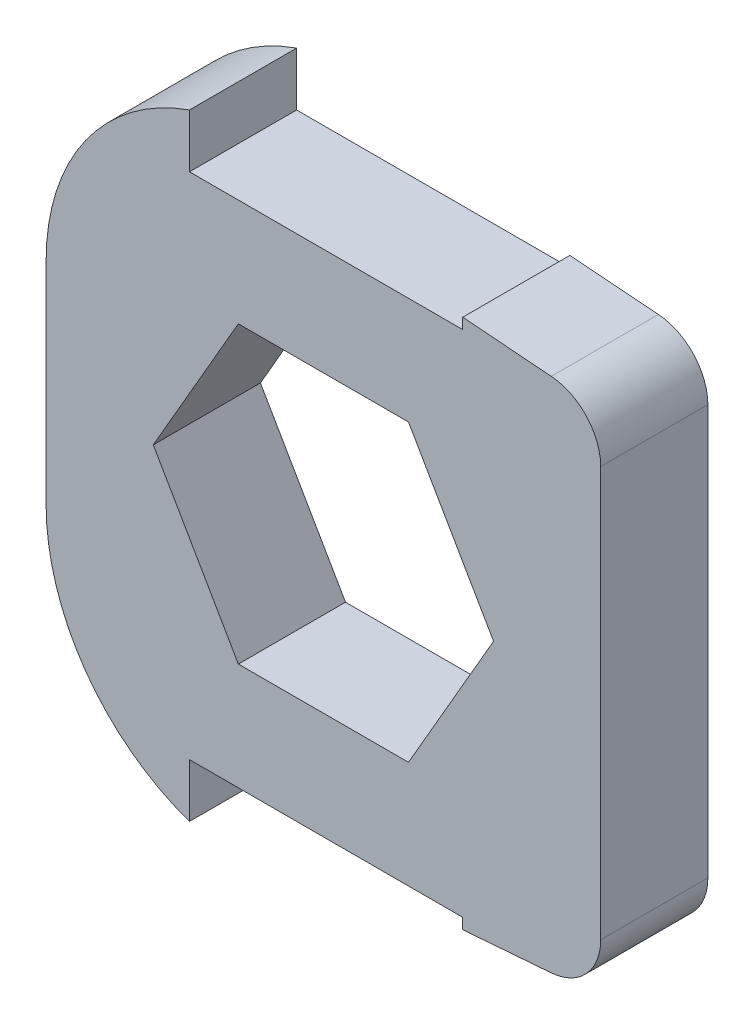
SolidWorks part; units mm, degrees
ref_plane "Plan de face" through (0, 0, 0) normal (0, 0, 1) x (1, 0, 0)
ref_plane "Plan de dessus" through (0, 0, 0) normal (0, 1, 0) x (1, 0, 0)
ref_plane "Plan de droite" through (0, 0, 0) normal (1, 0, 0) x (0, 0, -1)
sketch "Esquisse1" plane through (0, 0, 0) normal (0, 0, 1) x (1, 0, 0)
  line L0 (0, 5.75) -> (2.6754, 5.75)
  line L1 (2.6754, 5.75) -> (2.6754, 4.75)
  line L2 (2.6754, 4.75) -> (10.3509, 4.75) construction
  line L3 (10.3509, 4.75) -> (10.3509, -4.75)
  line L4 (10.3509, -4.75) -> (2.6754, -4.75) construction
  line L5 (2.6754, -4.75) -> (2.6754, -5.75)
  line L6 (2.6754, -5.75) -> (0, -5.75)
  line L7 (0, -5.75) -> (0, 5.75)
  line L8 (0, 0) -> (10.3509, 0) construction
  line L9 (10.3509, 4.75) -> (7.7754, 4.95)
  line L10 (2, 0) -> (3.5877, -2.75)
  line L11 (3.5877, -2.75) -> (6.7631, -2.75)
  line L12 (6.7631, -2.75) -> (8.3509, 0)
  line L13 (8.3509, 0) -> (6.7631, 2.75)
  line L14 (6.7631, 2.75) -> (3.5877, 2.75)
  line L15 (3.5877, 2.75) -> (2, 0)
  line L16 (7.7754, 4.95) -> (7.7754, 4.75)
  line L17 (7.7754, 4.75) -> (2.6754, 4.75)
  line L18 (7.7754, -4.75) -> (2.6754, -4.75)
  line L19 (7.7754, -4.95) -> (7.7754, -4.75)
  line L20 (10.3509, -4.75) -> (7.7754, -4.95)
  circle A0 centre (5.1754, 0) radius 2.75 construction
  point P22 (0, 0)
  dimension "D1" = 5.5
  dimension "D2" = 2
  dimension "D3" = 2.5
  dimension "D4" = 2
  dimension "D5" = 1
  dimension "D6" = 2
  dimension "D7" = 6.3509
  dimension "D8" = 5.1
  dimension "D9" = 0.2
  dimension "D10" = 9.5
extrude "Boss.-Extru.1" add sketch "Esquisse1" along normal blind 2
fillet "Congé1" radius 4 2 edges at (0, -5.75, 1) (0, 5.75, 1)
fillet "Congé2" radius 1 2 edges at (10.3509, -4.75, 1) (10.3509, 4.75, 1)
